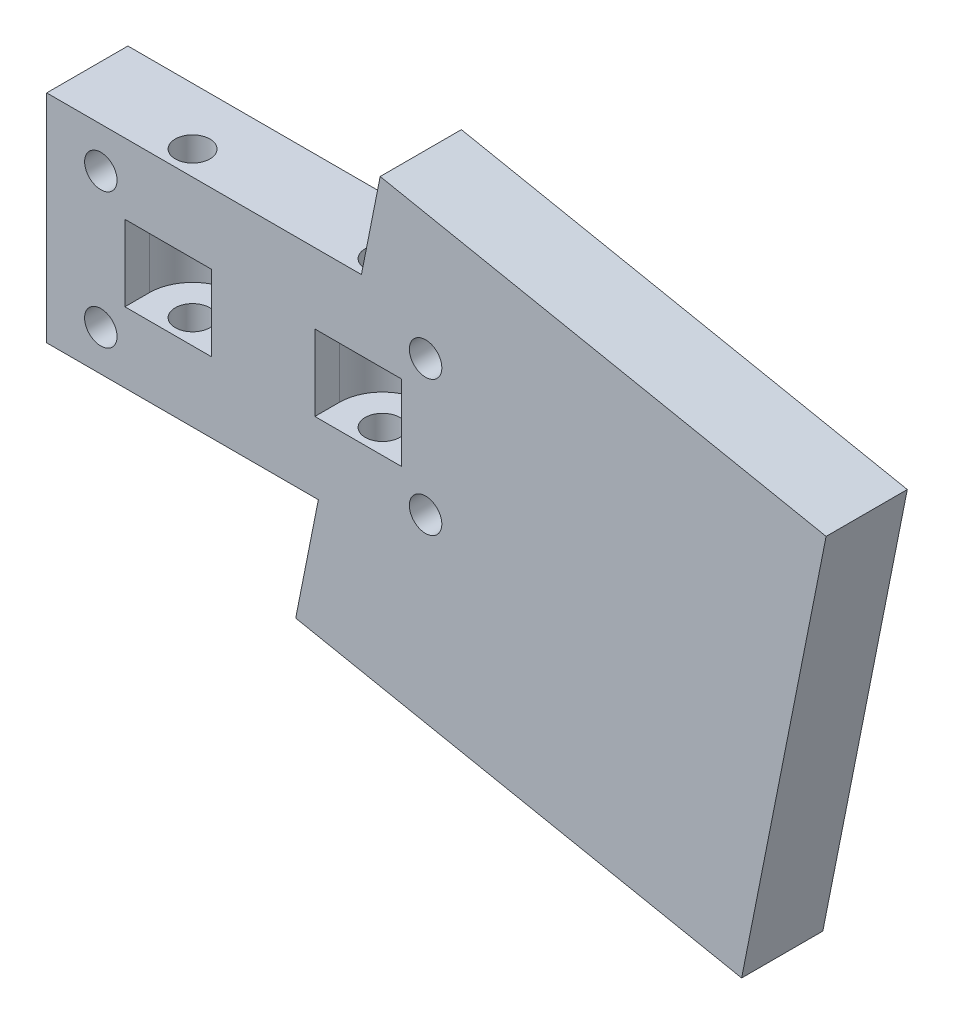
SolidWorks part; units mm, degrees
ref_plane "Front Plane" through (0, 0, 0) normal (0, 0, 1) x (1, 0, 0)
ref_plane "Top Plane" through (0, 0, 0) normal (0, 1, 0) x (1, 0, 0)
ref_plane "Right Plane" through (0, 0, 0) normal (1, 0, 0) x (0, 0, -1)
sketch "Sketch1" plane through (0, 0, 0) normal (0, 0, 1) x (1, 0, 0)
  line L2 (-38.1, -12.7) -> (-38.1, 12.7)
  line L3 (-38.1, 12.7) -> (38.1, 12.7)
  line L10 (38.1, -12.7) -> (38.1, 12.7)
  line L11 (-38.1, -12.7) -> (38.1, -12.7)
  line L14 (-38.1, 12.7) -> (38.1, -12.7) construction
  point P2 (0, 0)
  dimension "D1" = 76.2
  dimension "D2" = 25.4
extrude "Boss-Extrude1" add sketch "Sketch1" along normal blind 9.525
sketch "Sketch6" plane through (0, 0, 9.525) normal (0, 0, -1) x (-1, 0, 0)
  line L4 (8.8878, -26.0589) -> (-43.4272, -36.465)
  line L6 (8.8878, -26.0589) -> (-1.0228, 23.765)
  line L23 (-43.4272, -36.465) -> (-53.3378, 13.3589)
  line L24 (-1.0228, 23.765) -> (-53.3378, 13.3589)
  line L25 (8.8878, -26.0589) -> (-53.3378, 13.3589) construction
  line L26 (-43.4272, -36.465) -> (-1.0228, 23.765) construction
  line L27 (-38.1, 12.7) -> (38.1, 12.7) construction
  point P0 (-12.9798, -2.2819)
  point P1 (-22.225, -6.35)
  dimension "D1" = 53.34
  dimension "D2" = 50.8
  dimension "D3" = 11.25
  dimension "D4" = 6.35
  dimension "D5" = 22.225
extrude "Boss-Extrude2" add sketch "Sketch6" along normal up to surface (9.525 mm away) up to face at (0, 0, 0)
sketch "Sketch4" plane through (0, 0, 0) normal (0, 1, 0) x (1, 0, 0)
  line L7 (-1.1782, -9.525) -> (-38.1, -9.525) construction
  line L8 (-28.9242, -6.6675) -> (-28.9242, -9.525)
  line L9 (-18.7643, -6.6675) -> (-18.7642, -9.525)
  line L10 (-18.7642, -9.525) -> (-28.9242, -9.525)
  line L11 (-38.1, -9.525) -> (-38.1, 0) construction
  arc A2 (-18.7643, -6.6675) -> (-28.9242, -6.6675) centre (-23.8442, -6.6675) ccw
  dimension "D1" = 10.16
  dimension "D2" = 2.8575
  dimension "D3" = 14.2558
extrude "Cut-Extrude2" cut sketch "Sketch4" against normal mid plane 8.89
ref_plane "Plane3" through (-12.7, 0, 0) normal (-1, 0, 0) x (0, 0, 1)
sketch "Sketch2" plane through (0, 0, 9.525) normal (0, 0, 1) x (1, 0, 0)
  line L0 (-38.1, -12.7) -> (-6.2306, -12.7) construction
  line L1 (-38.1, 12.7) -> (-38.1, -12.7) construction
  circle A0 centre (-31.75, 7.9375) radius 1.905
  dimension "D1" = 3.81
  dimension "D2" = 20.6375
  dimension "D3" = 6.35
extrude "Cut-Extrude1" cut sketch "Sketch2" against normal up to surface (9.525 mm away) up to face at (0.6614, -3.175, 0)
sketch "Sketch5" plane through (0, 12.7, 0) normal (0, 1, 0) x (1, 0, 0)
  line L0 (-1.1782, -9.525) -> (-38.1, -9.525) construction
  line L1 (-38.1, -9.525) -> (-38.1, 0) construction
  circle A0 centre (-23.8442, -6.6675) radius 2.032
  dimension "D3" = 4.064
  dimension "D1" = 2.8575
  dimension "D2" = 14.2558
extrude "Cut-Extrude3" cut sketch "Sketch5" along normal blind 3.175 and the other way through all
mirror "Mirror1" about plane through (0, 0, 0) normal (0, 1, 0) of "Cut-Extrude1"
mirror "Mirror2" about plane through (-12.7, 0, 0) normal (-1, 0, 0) of "Mirror1", "Cut-Extrude3", "Cut-Extrude2"
